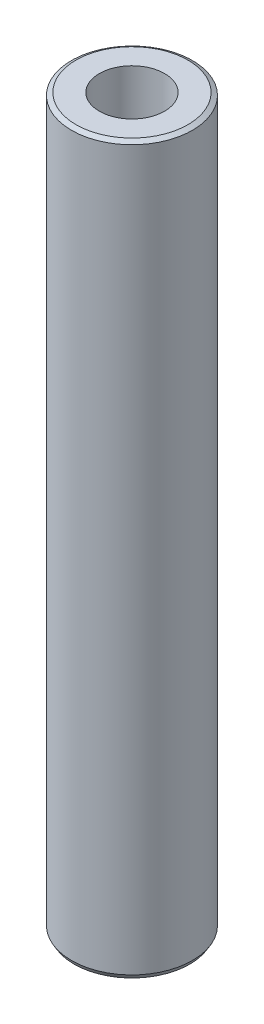
SolidWorks part; units mm, degrees
ref_plane "Front Plane" through (0, 0, 0) normal (0, 0, 1) x (1, 0, 0)
ref_plane "Top Plane" through (0, 0, 0) normal (0, 1, 0) x (1, 0, 0)
ref_plane "Right Plane" through (0, 0, 0) normal (1, 0, 0) x (0, 0, -1)
sketch "Sketch1" plane through (0, 0, 0) normal (0, 1, 0) x (1, 0, 0)
  circle A0 centre (0, 0) radius 12.5
  dimension "SHAFT_OD" = 25
extrude "Boss-Extrude1" add sketch "Sketch1" along normal blind 150.0497
sketch "Sketch2" plane through (0, 0, 0) normal (0, 1, 0) x (1, 0, 0)
  circle A0 centre (0, 0) radius 6.7471
  dimension "BORE_D" = 13.4943
extrude "Cut-Extrude1" cut sketch "Sketch2" along normal through all
chamfer "Chamfer1" distance 0.5378 angle 60 2 edges at (0, 150.0497, 12.5) (0, 0, 12.5) first distance on face at (0, 150.0497, 12.5) first distance on face at (0, 0, 6.7471)
